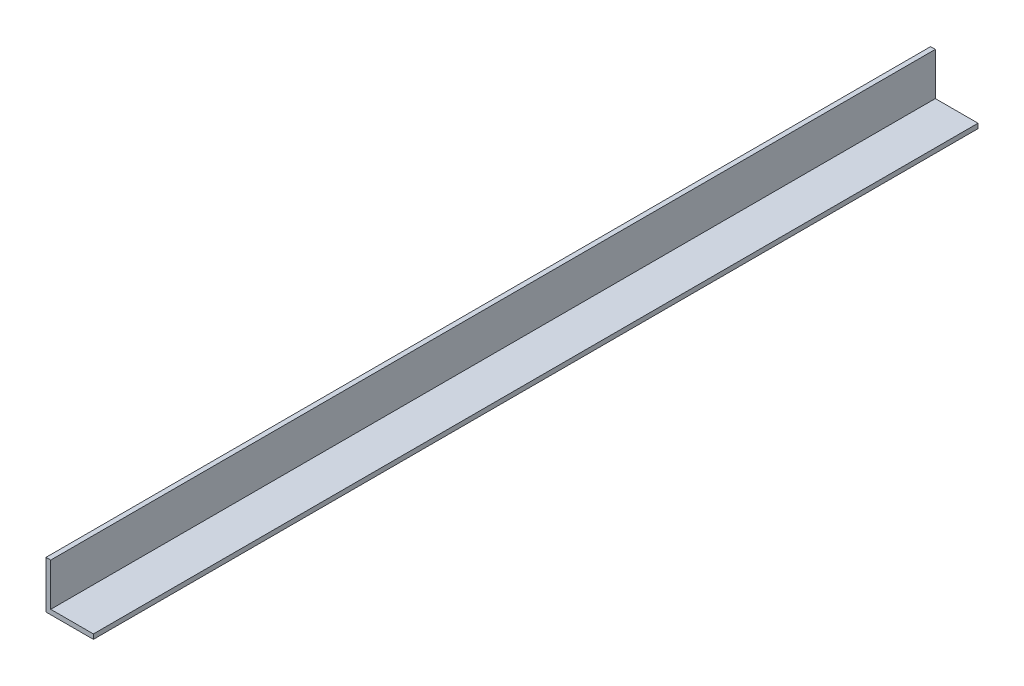
SolidWorks part; units mm, degrees
ref_plane "Front Plane" through (0, 0, 0) normal (0, 0, 1) x (1, 0, 0)
ref_plane "Top Plane" through (0, 0, 0) normal (0, 1, 0) x (1, 0, 0)
ref_plane "Right Plane" through (0, 0, 0) normal (1, 0, 0) x (0, 0, -1)
sketch "Sketch1" plane through (0, 0, 0) normal (0, 0, 1) x (1, 0, 0)
  line L0 (0, 0) -> (15, 0)
  line L1 (15, 0) -> (15, 1.5)
  line L2 (15, 1.5) -> (1.5, 1.5)
  line L3 (1.5, 1.5) -> (1.5, 15)
  line L4 (1.5, 15) -> (0, 15)
  line L5 (0, 15) -> (0, 0)
extrude "Boss-Extrude1" add sketch "Sketch1" along normal blind 280
